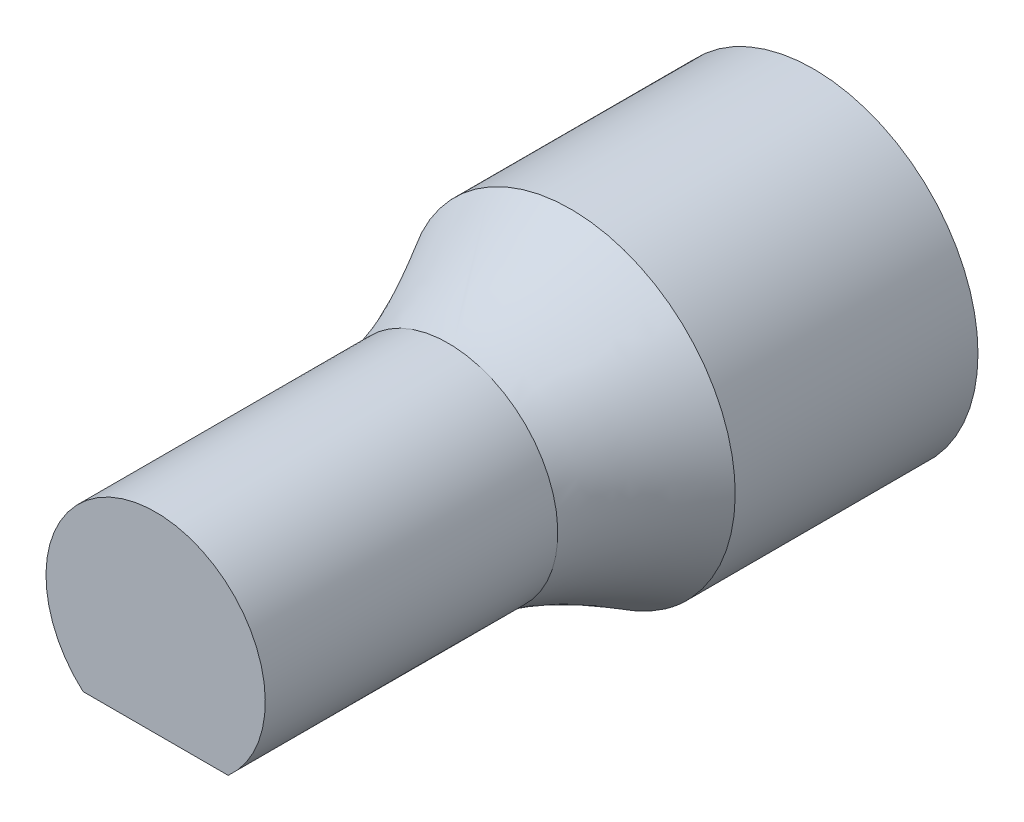
SolidWorks part; units mm, degrees
ref_plane "Front Plane" through (0, 0, 0) normal (0, 0, 1) x (1, 0, 0)
ref_plane "Top Plane" through (0, 0, 0) normal (0, 1, 0) x (1, 0, 0)
ref_plane "Right Plane" through (0, 0, 0) normal (1, 0, 0) x (0, 0, -1)
sketch "Sketch1" plane through (0, 0, 0) normal (0, 0, 1) x (1, 0, 0)
  circle A0 centre (0, 0) radius 9.525
  circle A1 centre (0, -0.79) radius 5.555
  dimension "D2" = 19.05
  dimension "D3" = 11.11
  dimension "D1" = 0.79
extrude "Boss-Extrude1" add sketch "Sketch1" along normal blind 14.06
sketch "Sketch2" plane through (0, 0, 14.06) normal (0, 0, 1) x (1, 0, 0)
  circle A0 centre (0, 0) radius 9.525
ref_plane "Plane1" through (0, 0, 21.16) normal (0, 0, 1) x (1, 0, 0)
sketch "Sketch3" plane through (0, 0, 21.16) normal (0, 0, 1) x (1, 0, 0)
  circle A0 centre (0, 0) radius 6.35
  dimension "D1" = 12.7
loft "Loft1" add profiles "Sketch2", "Sketch3" connector at (-4.6306, 8.3237, 14.06) connector at (0.2792, 6.3439, 21.16)
extrude "Boss-Extrude2" add sketch "Sketch3<2>" along normal blind 16.94
sketch "Sketch3<2>" plane through (0, 0, 21.16) normal (0, 0, 1) x (1, 0, 0) same geometry as "Sketch3"
sketch "Sketch4" plane through (0, 0, 38.1) normal (0, 0, 1) x (1, 0, 0)
  line L0 (-4.203, -4.76) -> (4.203, -4.76)
  circle A0 centre (0, 0) radius 6.35 construction
  circle M2 centre (0, 0) radius 6.35
  dimension "D1" = 4.76
extrude "Cut-Extrude1" cut sketch "Sketch4" against normal blind 5.56 and the other way through all contours L0 M2 region at (0, -5.4034, 38.1)
sketch "Sketch5" plane through (0, 0, 0) normal (0, 1, 0) x (1, 0, 0)
  circle A0 centre (0, -6.35) radius 1.19
  dimension "D1" = 2.38
  dimension "D2" = 6.35
extrude "Cut-Extrude2" cut sketch "Sketch5" against normal blind 10
sketch "Sketch6" plane through (0, 0, 0) normal (0, 0, -1) x (-1, 0, 0)
  line L0 (-3.8855, -4.76) -> (3.8855, -4.76)
  circle A0 centre (0, -0.79) radius 5.555 construction
  circle A1 centre (0, -0.79) radius 5.555 construction
  circle A2 centre (0, -0.79) radius 5.555
  circle M4 centre (0, -0.79) radius 5.555
  dimension "D1" = 4.76
extrude "Boss-Extrude3" add sketch "Sketch6" against normal up to next contours L0 M4 region at (0, -5.4025, 0)
